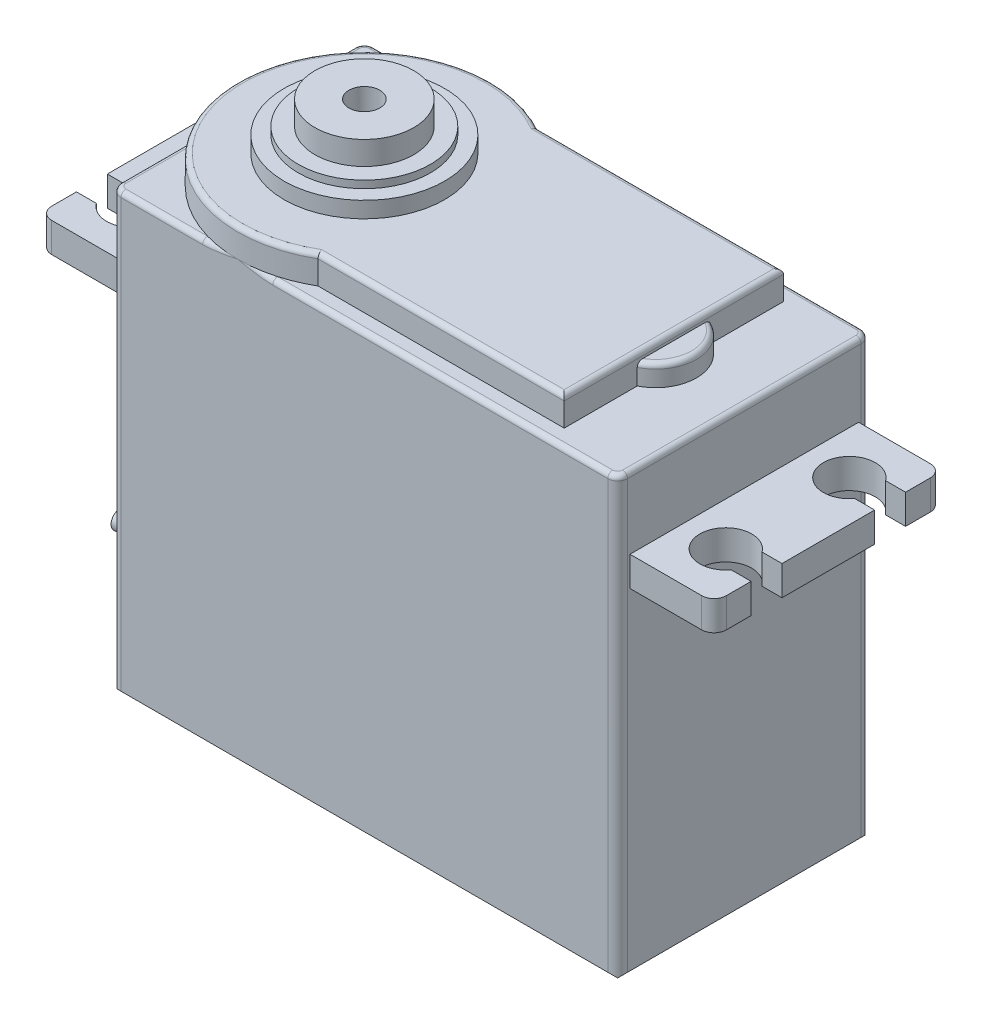
SolidWorks part; units mm, degrees
material "PE High Density"
ref_plane "Front Plane" through (0, 0, 0) normal (0, 0, 1) x (1, 0, 0)
ref_plane "Top Plane" through (0, 0, 0) normal (0, 1, 0) x (1, 0, 0)
ref_plane "Right Plane" through (0, 0, 0) normal (1, 0, 0) x (0, 0, -1)
sketch "Sketch1" plane through (0, 0, 0) normal (0, 1, 0) x (1, 0, 0)
  line L1 (-20.5, -10.25) -> (20.5, -10.25)
  line L2 (-20.5, -10.25) -> (-20.5, 10.25)
  line L3 (-20.5, 10.25) -> (20.5, 10.25)
  line L4 (20.5, -10.25) -> (20.5, 10.25)
  line L5 (-20.5, -10.25) -> (20.5, 10.25) construction
  line L6 (-20.5, 10.25) -> (20.5, -10.25) construction
  point P0 (0, 0)
  dimension "D1" = 41
  dimension "D2" = 20.5
extrude "Boss-Extrude1" add sketch "Sketch1" along normal blind 37
sketch "Sketch2" plane through (0, 37, 0) normal (0, 1, 0) x (1, 0, 0)
  line L0 (-20.5, 10.25) -> (-20.5, -10.25) construction
  line L1 (20.5, -10.25) -> (20.5, 10.25) construction
  line L2 (-5.122, -8.875) -> (14.8, -8.875)
  line L4 (-5.122, 8.875) -> (14.8, 8.875)
  line L5 (14.8, -8.875) -> (14.8, -2.9672)
  line L9 (14.8, 2.9672) -> (14.8, 8.875)
  arc A0 (-5.122, 8.875) -> (-5.122, -8.875) centre (-10.25, 0) ccw
  arc A1 (14.8, -2.9672) -> (14.8, 2.9672) centre (13.3208, 0) ccw
  point P5 (4.4919, 0)
  dimension "D1" = 10.25
  dimension "D2" = 17.75
  dimension "D3" = 5.7
extrude "Boss-Extrude2" add sketch "Sketch2" along normal blind 2.3
sketch "Sketch3" plane through (0, 39.3, 0) normal (0, 1, 0) x (1, 0, 0)
  circle A0 centre (-10.25, 0) radius 6.5
  dimension "D1" = 13
extrude "Boss-Extrude3" add sketch "Sketch3" along normal blind 1.3
sketch "Sketch4" plane through (0, 40.6, 0) normal (0, 1, 0) x (1, 0, 0)
  circle A0 centre (-10.25, 0) radius 5.35
  dimension "D1" = 10.7
extrude "Boss-Extrude4" add sketch "Sketch4" along normal blind 0.6
sketch "Sketch5" plane through (0, 39.3, 0) normal (0, 1, 0) x (1, 0, 0)
  line L0 (14.8, 2.9672) -> (14.8, -2.9672)
  arc A0 (14.8, -2.9672) -> (14.8, 2.9672) centre (13.3208, 0) ccw construction
  arc A1 (14.8, -2.9672) -> (14.8, 2.9672) centre (13.3208, 0) ccw
extrude "Cut-Extrude1" cut sketch "Sketch5" against normal blind 0.6
sketch "Sketch6" plane through (0, 41.2, 0) normal (0, 1, 0) x (1, 0, 0)
  circle A0 centre (-10.25, 0) radius 4
  dimension "D1" = 8
extrude "Boss-Extrude5" add sketch "Sketch6" along normal blind 1.9
chamfer "Chamfer1" distance 2 angle 45 4 edges at (-20.5, 0, 0) (0, 0, -10.25) (20.5, 0, 0) (0, 0, 10.25)
fillet "Fillet2" radius 0.8 4 edges at (-20.5, 19.5, -10.25) (-20.5, 19.5, 10.25) (20.5, 19.5, -10.25) (20.5, 19.5, 10.25)
sketch "Sketch7" plane through (-20.5, 0, 0) normal (-1, 0, 0) x (0, 0, 1)
  line L1 (-9.25, 31.2) -> (9.25, 31.2)
  line L2 (-9.25, 31.2) -> (-9.25, 28.8)
  line L3 (-9.25, 28.8) -> (9.25, 28.8)
  line L4 (9.25, 31.2) -> (9.25, 28.8)
  line L6 (-9.45, 37) -> (0, 37) construction
  line L9 (-10.25, 37) -> (-10.25, 2) construction
  dimension "D1" = 5.8
  dimension "D2" = 2.4
  dimension "D3" = 18.5
  dimension "D4" = 1
extrude "Boss-Extrude6" add sketch "Sketch7" along normal blind 6.8
sketch "Sketch9" plane through (0, 31.2, 0) normal (0, 1, 0) x (1, 0, 0)
  line L0 (-27.3, -9.25) -> (-27.3, 9.25) construction
  line L3 (-25.6875, 6.25) -> (-27.3, 6.25)
  line L4 (-21.6, 3.75) -> (-22.3125, 3.75)
  line L5 (-21.6, 3.75) -> (-21.6, 6.25)
  line L6 (-21.6, 6.25) -> (-22.3125, 6.25)
  line L7 (-27.3, 3.75) -> (-27.3, 6.25)
  line L8 (-21.6, 3.75) -> (-24, 5) construction
  line L9 (-21.6, 6.25) -> (-24, 5) construction
  line L10 (-21.6, -6.25) -> (-27.3, -6.25)
  line L11 (-21.6, -6.25) -> (-21.6, -3.75)
  line L12 (-21.6, -3.75) -> (-27.3, -3.75)
  line L13 (-27.3, -6.25) -> (-27.3, -3.75)
  line L14 (-21.6, -6.25) -> (-24, -5) construction
  line L15 (-21.6, -3.75) -> (-24, -5) construction
  line L18 (-25.6875, 3.75) -> (-27.3, 3.75)
  arc A0 (-25.6875, 3.75) -> (-25.6875, 6.25) centre (-24, 5) ccw
  arc A1 (-25.6875, -6.25) -> (-25.6875, -3.75) centre (-24, -5) ccw
  line M4 (-27.3, 9.25) -> (-27.3, -9.25)
  dimension "D1" = 4.2
  dimension "D2" = 4.2
  dimension "D3" = 3.3
  dimension "D4" = 10
  dimension "D5" = 5
  dimension "D6" = 2.5
  dimension "D7" = 2.5
  dimension "D8" = 3.3
extrude "Cut-Extrude2" cut sketch "Sketch9" against normal blind 6.8 contours A0 L3 L18 M4 | L12 A1 | L10 A1 | L10 A1 L12 M4 region at (-24.5093, 31.2, -5) region at (-24.6644, 31.2, 5) region at (-24, 31.2, 3.4033) region at (-24, 31.2, 6.5967)
fillet "Fillet1" radius 1 2 edges at (-27.3, 30, 9.25) (-27.3, 30, -9.25)
sketch "Sketch10" plane through (0, 31.2, 0) normal (0, 1, 0) x (1, 0, 0)
  line L0 (-20.5, -9.25) -> (-20.5, 9.25) construction
  line L1 (-27.3, -0.5) -> (-20.5, -0.5)
  line L2 (-27.3, -0.5) -> (-27.3, 0.5)
  line L3 (-27.3, 0.5) -> (-20.5, 0.5)
  line L4 (-20.5, -0.5) -> (-20.5, 0.5)
  line L5 (-27.3, -0.5) -> (-20.5, 0.5) construction
  line L6 (-27.3, 0.5) -> (-20.5, -0.5) construction
  line L7 (-27.3, -3.75) -> (-27.3, 3.75) construction
  point P0 (-23.9, 0)
  dimension "D1" = 1
extrude "Boss-Extrude7" add sketch "Sketch10" along normal blind 1.5
sketch "Sketch11" plane through (0, 0, 0.5) normal (0, 0, 1) x (1, 0, 0)
  line L0 (-27.3, 31.2) -> (-20.5, 32.7)
  line L1 (-20.5, 32.7) -> (-27.3, 32.7)
  line L2 (-27.3, 32.7) -> (-27.3, 31.2)
extrude "Cut-Extrude3" cut sketch "Sketch11" against normal blind 1.5
ref_plane "Plane1" through (0, 0, 0) normal (-1, 0, 0) x (0, 0, 1)
mirror "Mirror2" about plane through (0, 0, 0) normal (-1, 0, 0) of "Cut-Extrude3", "Boss-Extrude7", "Fillet1", "Cut-Extrude2", "Boss-Extrude6"
sketch "Sketch12" plane through (0, 43.1, 0) normal (0, 1, 0) x (1, 0, 0)
  circle A0 centre (-10.25, 0) radius 1.25
  dimension "D1" = 2.5
extrude "Cut-Extrude4" cut sketch "Sketch12" against normal blind 4
fillet "Fillet5" radius 0.4 5 edges at (16.6363, 38.7, 0) (14.8, 39.3, 0) (4.839, 39.3, -8.875) (-20.5, 39.3, 0) (4.839, 39.3, 8.875)
fillet "Fillet7" radius 0.4 11 edges at (20.2657, 37, 10.0157) (4.725, 37, 10.25) (-14.975, 37, 10.25) (-20.2657, 37, 10.0157) (-20.5, 37, 4.725) (-20.5, 37, -4.725) (-20.2657, 37, -10.0157) (-14.975, 37, -10.25) (4.725, 37, -10.25) (20.2657, 37, -10.0157) (20.5, 37, 0)
sketch "Sketch13" plane through (-20.5, 0, 0) normal (-1, 0, 0) x (0, 0, 1)
  line L0 (8.25, 0) -> (-8.25, 0) construction
  line L1 (-3.5, 3.2) -> (3.5, 3.2)
  line L2 (-3.5, 3.2) -> (-3.5, 7.4)
  line L3 (-3.5, 7.4) -> (3.5, 7.4)
  line L4 (3.5, 3.2) -> (3.5, 7.4)
  line L5 (-3.5, 3.2) -> (3.5, 7.4) construction
  line L6 (-3.5, 7.4) -> (3.5, 3.2) construction
  point P0 (0, 5.3)
  dimension "D1" = 7
  dimension "D2" = 4.2
  dimension "D3" = 3.2
extrude "Boss-Extrude8" add sketch "Sketch13" along normal blind 1
sketch "Sketch14" plane through (-21.5, 0, 0) normal (-1, 0, 0) x (0, 0, 1)
  line L9 (3.15, 3.55) -> (3.15, 7.05)
  line L10 (3.15, 7.05) -> (-3.15, 7.05)
  line L11 (-3.15, 7.05) -> (-3.15, 3.55)
  line L12 (-3.15, 3.55) -> (3.15, 3.55)
  line L13 (3.15, 3.55) -> (3.15, 7.05)
  line L14 (3.15, 7.05) -> (-3.15, 7.05)
  line L15 (-3.15, 7.05) -> (-3.15, 3.55)
  line L16 (-3.15, 3.55) -> (3.15, 3.55)
  dimension "D1" = 0.35
extrude "Boss-Extrude9" add sketch "Sketch14" along normal blind 4 draft 5 contours L14 L15 L16 L13
sketch "Sketch15" plane through (-25.5, 0, 0) normal (-1, 0, 0) x (0, 0, 1)
  line L0 (-2.8, 3.9) -> (2.8, 3.9) construction
  circle A0 centre (-1.5, 5.3) radius 0.75
  circle A1 centre (0, 5.3) radius 0.75
  circle A2 centre (1.5, 5.3) radius 0.75
  dimension "D1" = 1.5
  dimension "D2" = 1.5
  dimension "D3" = 1.5
  dimension "D4" = 1.4
extrude "Boss-Extrude12" add sketch "Sketch15" along normal blind 3 separate body contours A0 | A1 | A2 region at (-25.5, 5.3, -1.5) region at (-25.5, 5.3, 1.5) region at (-25.5, 5.3, 0)
sketch "Croquis3" plane through (0, 39.1, 0) normal (0, 1, 0) x (1, 0, 0)
  line L0 (-10.25, 0) -> (-10.25, 19.3609) construction
sketch "Croquis5" plane through (0, 39.1, 0) normal (0, 1, 0) x (1, 0, 0)
  line L0 (-10.25, -0.5457) -> (-10.25, 0.5457)
  line L1 (-10.25, 0) -> (-10.25, 19.3609) construction
  line L2 (-10.25, -0.5457) -> (-9.894, -0.5457)
  line L3 (-9.894, -0.5457) -> (-9.894, 0.5457)
  line L4 (-9.894, 0.5457) -> (-10.25, 0.5457)
  point P6 (-10.25, 0)
extrude "Saliente-Extruir1" add sketch "Croquis5" along normal blind 10
sketch "Croquis6" plane through (-10.25, 0, 0) normal (-1, 0, 0) x (0, 0, 1)
  line L0 (0, 39.1) -> (0, 189.1429) construction
  line L1 (0, 39.1) -> (0, -42.7671) construction
  line L2 (0, -42.7671) -> (0, 189.1429) construction
sketch "Croquis7" plane through (0, 49.1, 0) normal (0, 1, 0) x (1, 0, 0)
  line L0 (-10.25, -0.5457) -> (-9.894, -0.5457)
  line L1 (-9.894, -0.5457) -> (-9.894, 0.5457)
  line L2 (-9.894, 0.5457) -> (-10.25, 0.5457)
  line L3 (-10.25, 0.5457) -> (-10.25, -0.5457)
extrude "Cortar-Extruir1" cut sketch "Croquis7" against normal blind 9.9
sketch "Croquis8" plane through (0, 0, 0.5) normal (0, 0, 1) x (1, 0, 0)
  line L0 (-20.5, 32.7) -> (-20.5, 31.2)
  line L1 (-20.5, 31.2) -> (-27.3, 31.2)
  line L2 (-27.3, 31.2) -> (-20.5, 32.7)
extrude "Cortar-Extruir2" cut sketch "Croquis8" against normal blind 10
sketch "Croquis9" plane through (0, 0, 0.5) normal (0, 0, 1) x (1, 0, 0)
  line L0 (20.5, 32.7) -> (20.5, 31.2)
  line L1 (20.5, 31.2) -> (27.3, 31.2)
  line L2 (27.3, 31.2) -> (20.5, 32.7)
extrude "Cortar-Extruir3" cut sketch "Croquis9" against normal blind 10
